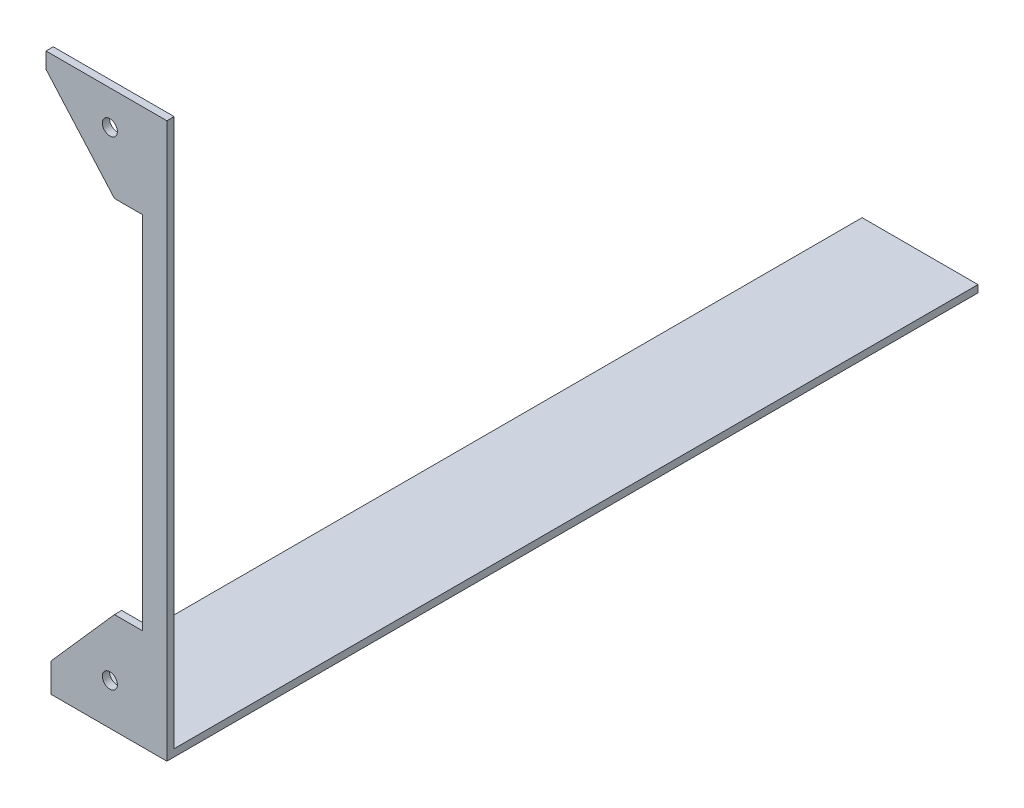
SolidWorks part; units mm, degrees
ref_plane "Front Plane" through (0, 0, 0) normal (0, 0, 1) x (1, 0, 0)
ref_plane "Top Plane" through (0, 0, 0) normal (0, 1, 0) x (1, 0, 0)
ref_plane "Right Plane" through (0, 0, 0) normal (1, 0, 0) x (0, 0, -1)
sketch "Sketch1" plane through (0, 0, 0) normal (0, 0, 1) x (1, 0, 0)
  line L0 (-250, 120) -> (0, 120) construction
  line L1 (0, 118) -> (0, 2) construction
  line L2 (0, 0) -> (-250, 0) construction
  line L3 (-26.5, 116.5) -> (-11.5, 99.5) construction
  line L4 (-11.5, 99.5) -> (-5.4, 99.5) construction
  line L5 (-5.4, 99.5) -> (-5.4, 20.5) construction
  line L6 (-11.5, 20.5) -> (-26.5, 3.5) construction
  line L7 (-5.4, 20.5) -> (-11.5, 20.5) construction
  line L8 (-26.5, 120) -> (0, 120)
  line L9 (0, 120) -> (0, 0)
  line L10 (0, 0) -> (-26.5, 0)
  line L11 (-26.5, 116.5) -> (-11.5, 99.5)
  line L12 (-11.5, 99.5) -> (-5.4, 99.5)
  line L13 (-5.4, 99.5) -> (-5.4, 20.5)
  line L14 (-11.5, 20.5) -> (-26.5, 3.5)
  line L15 (-5.4, 20.5) -> (-11.5, 20.5)
  line L16 (-26.5, 3.5) -> (-26.5, 0)
  line L17 (-26.5, 116.5) -> (-26.5, 120)
  line L18 (-25.4, 4.7467) -> (-25.4, 0)
  arc A0 (-14.15, 112.5) -> (-10.85, 112.5) centre (-12.5, 112.5) ccw construction
  arc A1 (-10.85, 112.5) -> (-14.15, 112.5) centre (-12.5, 112.5) ccw construction
  arc A2 (-14.15, 7.5) -> (-10.85, 7.5) centre (-12.5, 7.5) ccw construction
  arc A3 (-10.85, 7.5) -> (-14.15, 7.5) centre (-12.5, 7.5) ccw construction
  arc A4 (-14.15, 112.5) -> (-10.85, 112.5) centre (-12.5, 112.5) ccw
  arc A5 (-10.85, 112.5) -> (-14.15, 112.5) centre (-12.5, 112.5) ccw
  arc A6 (-14.15, 7.5) -> (-10.85, 7.5) centre (-12.5, 7.5) ccw
  arc A7 (-10.85, 7.5) -> (-14.15, 7.5) centre (-12.5, 7.5) ccw
  dimension "D1" = 25.4
extrude "Boss-Extrude1" add sketch "Sketch1" along normal blind 1.5875 contours L14 L18 L10 L9 L8 L17 L11 L12 L13 L15 A7 A6 A5 A4 region at (-13.25, 118.7711, 0)
sketch "Sketch2" plane through (0, 0, 0) normal (0, 1, 0) x (1, 0, 0)
  line L0 (0, -1.5875) -> (0, 176.2125)
  line L1 (0, 176.2125) -> (-25.4, 176.2125)
  line L2 (-25.4, 176.2125) -> (-25.4, -1.5875)
  line L4 (0, -1.5875) -> (-25.4, -1.5875) construction
  line L5 (0, -1.5875) -> (-25.4, -1.5875)
  dimension "D1" = 177.8
extrude "Boss-Extrude2" add sketch "Sketch2" against normal blind 1.5875
